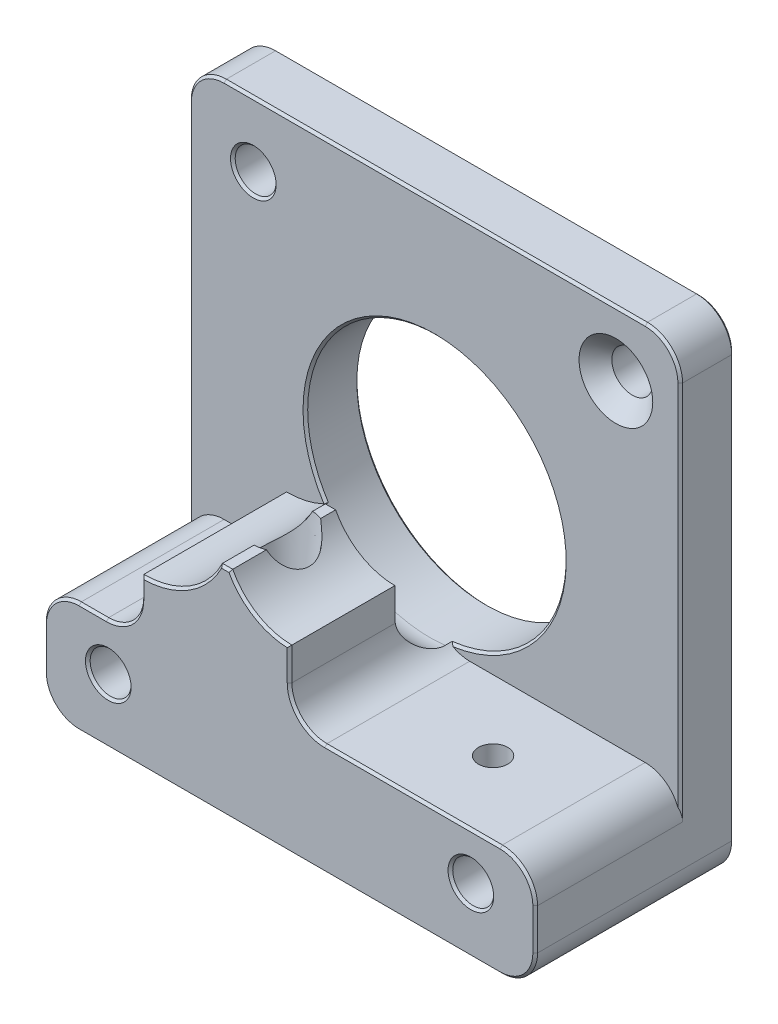
SolidWorks part; units mm, degrees
ref_plane "Спереди" through (0, 0, 0) normal (0, 0, 1) x (1, 0, 0)
ref_plane "Сверху" through (0, 0, 0) normal (0, 1, 0) x (1, 0, 0)
ref_plane "Справа" through (0, 0, 0) normal (1, 0, 0) x (0, 0, -1)
sketch "Эскиз1" plane through (0, 0, 0) normal (0, 0, 1) x (1, 0, 0)
  line L1 (0, 0) -> (42, 0)
  line L2 (0, 0) -> (0, 42)
  line L3 (0, 42) -> (42, 42)
  line L4 (42, 0) -> (42, 42)
  dimension "D1" = 42
  dimension "D2" = 42
extrude "Бобышка-Вытянуть1" add sketch "Эскиз1" along normal blind 17
sketch "Эскиз2" plane through (0, 0, 17) normal (0, 0, 1) x (1, 0, 0)
  line L0 (42, 0) -> (42, 42) construction
  line L1 (0, 42) -> (42, 42)
  line L2 (0, 42) -> (0, 9.5)
  line L3 (0, 9.5) -> (8.3371, 9.5)
  line L4 (42, 42) -> (42, 9.5)
  line L5 (0, 0) -> (42, 0) construction
  line L6 (21, 15.3) -> (21, 9.5)
  line L7 (8.3371, 9.5) -> (8.3371, 14.2)
  line L8 (21, 9.5) -> (42, 9.5)
  line L9 (15.9375, 18.3806) -> (15.0625, 18.3806)
  arc A0 (15.9375, 18.3806) -> (21, 15.3) centre (21, 21) ccw
  arc A1 (8.3371, 14.2) -> (15.0625, 18.3806) centre (8.3371, 21.7) ccw
  dimension "D2" = 0.875
  dimension "D5" = 7.5
  dimension "D6" = 5.7
  dimension "D1" = 9.5
  dimension "D3" = 21
  dimension "D4" = 8.3371
  dimension "D7" = 5.8
  dimension "D8" = 4.7
extrude "Вырез-Вытянуть1" cut sketch "Эскиз2" against normal blind 12.4
sketch "Эскиз3" plane through (0, 0, 0) normal (0, 0, -1) x (-1, 0, 0)
  circle A0 centre (-21, 21) radius 11.05
extrude "Вырез-Вытянуть2" cut sketch "Эскиз3" against normal blind 8
sketch "Эскиз4" plane through (0, 18.3806, 0) normal (0, 1, 0) x (1, 0, 0)
  circle A0 centre (15, -11.6) radius 2.5
extrude "Вырез-Вытянуть3" cut sketch "Эскиз4" against normal blind 22.2 draft 7
sketch "Эскиз5" plane through (0, 9.5, 0) normal (0, 1, 0) x (1, 0, 0)
  circle A0 centre (32, -10.6) radius 1.25
extrude "Вырез-Вытянуть4" cut sketch "Эскиз5" against normal blind 12.4
fillet "Скругление1" radius 3 8 edges at (42, 42, 2.3) (0, 42, 2.3) (42, 0, 8.5) (0, 0, 8.5) (0, 9.5, 10.8) (21, 9.5, 10.8) (8.3371, 9.5, 10.8) (42, 9.5, 10.8)
chamfer "Фаска1" distance 0.2 angle 45 9 edges at (0.8787, 41.1213, 0) (0, 21, 0) (0.8787, 0.8787, 0) (21, 0, 0) (41.1213, 0.8787, 0) (42, 21, 0) (41.1213, 41.1213, 0) (21, 42, 0) (9.95, 21, 0)
chamfer "Фаска2" distance 0.2 angle 45 21 edges at (0.8787, 0.8787, 17) (0, 4.75, 17) (0.8787, 8.6213, 17) (4.1685, 9.5, 17) (42, 4.75, 17) (41.1213, 0.8787, 17) (21, 0, 17) (42, 22.75, 4.6) (41.1213, 41.1213, 4.6) (21, 42, 4.6) (0.8787, 41.1213, 4.6) (0, 22.75, 4.6) (7.4584, 10.3787, 17) (8.3371, 13.35, 17) (12.2965, 15.3303, 17) (15.5, 18.3806, 17) (18.0369, 16.1307, 17) (21, 13.9, 17) (21.8787, 10.3787, 17) (31.5, 9.5, 17) (41.1213, 8.6213, 17)
chamfer "Фаска3" distance 0.2 angle 45 1 edges at (25.703, 30.9992, 4.6)
sketch "Эскиз6" plane through (0, 0, 0) normal (0, 0, -1) x (-1, 0, 0)
  circle A0 centre (-5.5, 36.5) radius 1.75
  circle A1 centre (-36.5, 36.5) radius 1.75
  circle A2 centre (-5.5, 5.5) radius 1.75
  circle A3 centre (-36.5, 5.5) radius 1.75
  dimension "D1" = 3.5
extrude "Вырез-Вытянуть5" cut sketch "Эскиз6" against normal blind 26
chamfer "Фаска4" distance 0.2 angle 45 8 edges at (3.75, 36.5, 0) (34.75, 36.5, 0) (34.75, 5.5, 0) (3.75, 5.5, 0) (3.75, 5.5, 17) (34.75, 5.5, 17) (38.25, 36.5, 4.6) (7.25, 36.5, 4.6)
fillet "Filete2" radius 3 1 edges at (16.297, 11.0008, 8)
hole_wizard "CSK for M3 Flat Head Machine Screw1" positions "Sketch2" profile "Sketch1" countersink size "M3" standard "ANSI Metric" end condition through all
sketch "Sketch2" plane through (0, 0, 4.6) normal (0, 0, 1) x (1, 0, 0)
  point P0 (36.5, 36.5)
sketch "Sketch1" plane through (36.5, 36.5, 4.6) normal (1, 0, 0) x (0, -1, 0)
  line L0 (0, 0) -> (0, 4.6)
  line L1 (0, 4.6) -> (1.6, 4.6)
  line L2 (1.6, 4.6) -> (1.6, 1.55)
  line L3 (1.6, 1.55) -> (3.15, 0)
  line L5 (3.15, 0) -> (0, 0)
  line L6 (-1.6, 1.55) -> (-3.15, 0) construction
  line L11 (0, -6.35) -> (0, 107.95) construction
  dimension "Thru Hole Dia." = 3.2
  dimension "Thru Hole Depth" = 4.6
  dimension "Near C'Sink Dia." = 6.3
  dimension "Near C'Sink Angle" = 90
hole_wizard "Tap Drill for M6 Tap2" positions "Sketch5" profile "Sketch6" hole size "M6" standard "ISO"
sketch "Sketch5" plane through (0, 0, 0) normal (0, -1, 0) x (-1, 0, 0)
  point P0 (-15, -11.6)
sketch "Sketch6" plane through (15, 0, 11.6) normal (1, 0, 0) x (0, 0, -1)
  line L0 (0, 0) -> (0, 7.5022)
  line L1 (0, 7.5022) -> (2.5, 6)
  line L2 (2.5, 6) -> (2.5, 0)
  line L5 (2.5, 0) -> (0, 0)
  line L10 (0, 7.5022) -> (-2.5, 6) construction
  line L11 (0, -6.35) -> (0, 107.95) construction
  dimension "Hole Dia." = 5
  dimension "Hole Depth" = 6
  dimension "Drill Angle" = 118
